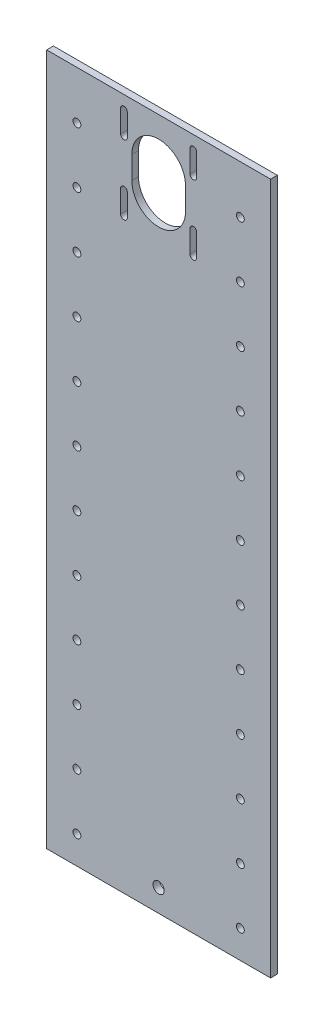
SolidWorks part; units mm, degrees
ref_plane "Plan de face" through (0, 0, 0) normal (0, 0, 1) x (1, 0, 0)
ref_plane "Plan de dessus" through (0, 0, 0) normal (0, 1, 0) x (1, 0, 0)
ref_plane "Plan de droite" through (0, 0, 0) normal (1, 0, 0) x (0, 0, -1)
sketch "Esquisse1" plane through (0, 0, 0) normal (0, 0, 1) x (1, 0, 0)
  line L1 (0, 0) -> (100, 0)
  line L2 (0, 0) -> (0, 309)
  line L3 (0, 309) -> (100, 309)
  line L4 (100, 0) -> (100, 309)
  dimension "D1" = 309
  dimension "D2" = 100
extrude "Boss.-Extru.1" add sketch "Esquisse1" along normal blind 3
sketch "Esquisse2" plane through (0, 0, 3) normal (0, 0, 1) x (1, 0, 0)
  line L0 (34.5, 293) -> (65.5, 262) construction
  line L1 (34.5, 293) -> (65.5, 293) construction
  line L2 (34.5, 293) -> (34.5, 262) construction
  line L3 (34.5, 262) -> (65.5, 262) construction
  line L4 (65.5, 293) -> (65.5, 262) construction
  line L5 (65.5, 293) -> (34.5, 262) construction
  line L6 (50, 277.5) -> (50, 287.5) construction
  line L7 (38, 277.5) -> (38, 287.5)
  line L8 (62, 277.5) -> (62, 287.5)
  line L9 (34.5, 293) -> (34.5, 303) construction
  line L10 (33, 293) -> (33, 303)
  line L11 (36, 293) -> (36, 303)
  line L12 (65.5, 293) -> (65.5, 303) construction
  line L13 (64, 293) -> (64, 303)
  line L14 (67, 293) -> (67, 303)
  line L15 (65.5, 262) -> (65.5, 272) construction
  line L16 (64, 262) -> (64, 272)
  line L17 (67, 262) -> (67, 272)
  line L18 (34.5, 262) -> (34.5, 272) construction
  line L19 (33, 262) -> (33, 272)
  line L20 (36, 262) -> (36, 272)
  line L21 (50, 293) -> (50, 309) construction
  line L22 (100, 309) -> (0, 309) construction
  line L23 (34.5, 303) -> (65.5, 303) construction
  arc A0 (38, 277.5) -> (62, 277.5) centre (50, 277.5) ccw
  arc A1 (62, 287.5) -> (38, 287.5) centre (50, 287.5) ccw
  arc A2 (33, 293) -> (36, 293) centre (34.5, 293) ccw
  arc A3 (36, 303) -> (33, 303) centre (34.5, 303) ccw
  arc A4 (64, 293) -> (67, 293) centre (65.5, 293) ccw
  arc A5 (67, 303) -> (64, 303) centre (65.5, 303) ccw
  arc A6 (64, 262) -> (67, 262) centre (65.5, 262) ccw
  arc A7 (67, 272) -> (64, 272) centre (65.5, 272) ccw
  arc A8 (33, 262) -> (36, 262) centre (34.5, 262) ccw
  arc A9 (36, 272) -> (33, 272) centre (34.5, 272) ccw
  point P4 (50, 282.5)
  point P11 (34.5, 298)
  point P17 (65.5, 298)
  point P23 (65.5, 267)
  point P29 (34.5, 267)
  dimension "D1" = 24
  dimension "D2" = 31
  dimension "D3" = 3
  dimension "D4" = 10
  dimension "D5" = 6
extrude "Persage Stepper" cut sketch "Esquisse2" against normal through all
sketch "Esquisse3" plane through (0, 0, 3) normal (0, 0, 1) x (1, 0, 0)
  line L0 (50, 10) -> (50, 0) construction
  line L1 (0, 0) -> (100, 0) construction
  circle A0 centre (50, 10) radius 2.5
  dimension "D1" = 5
  dimension "D2" = 10
extrude "Enlèv. mat.-Extru.1" cut sketch "Esquisse3" against normal up to surface (3 mm away) up to face at (34.5, 267, 0)
sketch "Esquisse4" plane through (0, 0, 3) normal (0, 0, 1) x (1, 0, 0)
  line L0 (50, 0) -> (50, 12.5) construction
  line L1 (0, 0) -> (100, 0) construction
  line L2 (13.5, 12.5) -> (86.5, 12.5) construction
  circle A0 centre (13.5, 12.5) radius 1.75
  circle A1 centre (86.5, 12.5) radius 1.75
  circle A2 centre (13.5, 37.5) radius 1.75
  circle A3 centre (86.5, 37.5) radius 1.75
  circle A4 centre (13.5, 62.5) radius 1.75
  circle A5 centre (86.5, 62.5) radius 1.75
  circle A6 centre (13.5, 87.5) radius 1.75
  circle A7 centre (86.5, 87.5) radius 1.75
  circle A8 centre (13.5, 112.5) radius 1.75
  circle A9 centre (86.5, 112.5) radius 1.75
  circle A10 centre (13.5, 137.5) radius 1.75
  circle A11 centre (86.5, 137.5) radius 1.75
  circle A12 centre (13.5, 162.5) radius 1.75
  circle A13 centre (86.5, 162.5) radius 1.75
  circle A14 centre (13.5, 187.5) radius 1.75
  circle A15 centre (86.5, 187.5) radius 1.75
  circle A16 centre (13.5, 212.5) radius 1.75
  circle A17 centre (86.5, 212.5) radius 1.75
  circle A18 centre (13.5, 237.5) radius 1.75
  circle A19 centre (86.5, 237.5) radius 1.75
  circle A20 centre (13.5, 262.5) radius 1.75
  circle A21 centre (86.5, 262.5) radius 1.75
  circle A22 centre (13.5, 287.5) radius 1.75
  circle A23 centre (86.5, 287.5) radius 1.75
  point P7 (50, 12.5)
  dimension "D2" = 3.5
  dimension "D3" = 3.5
  dimension "D1" = 73
  dimension "D4" = 12.5
  dimension "D5" = 12
extrude "Enlèv. mat.-Extru.2" cut sketch "Esquisse4" against normal up to surface (3 mm away) up to face at (47.5, 10, 0)
